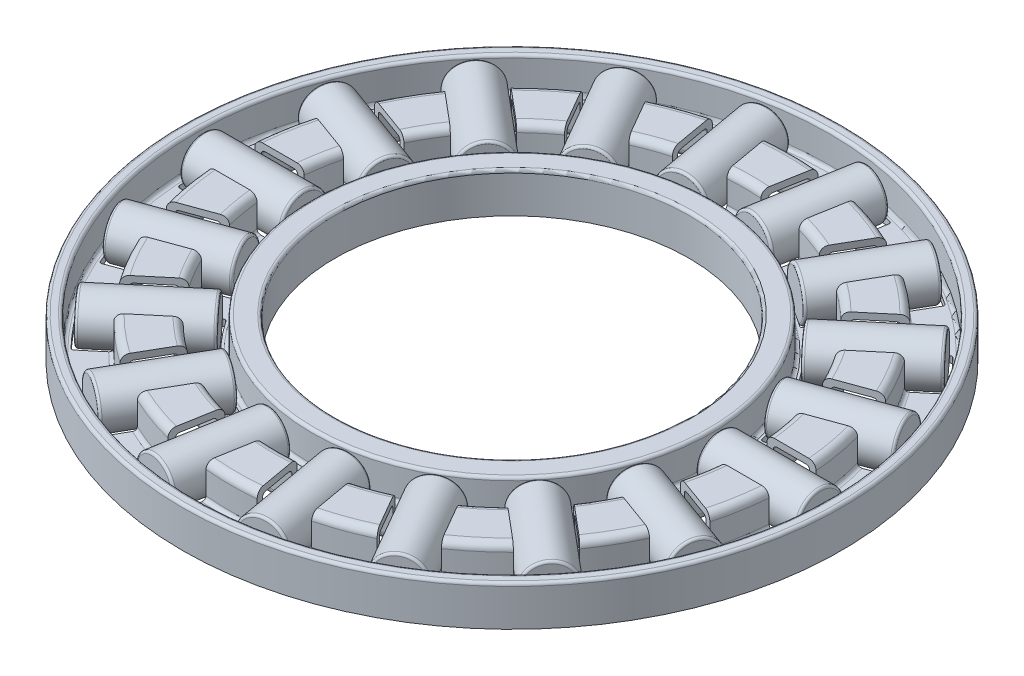
SolidWorks part; units mm, degrees
material "Plain Carbon Steel"
ref_plane "Front Plane" through (0, 0, 0) normal (0, 0, 1) x (1, 0, 0)
ref_plane "Top Plane" through (0, 0, 0) normal (0, 1, 0) x (1, 0, 0)
ref_plane "Right Plane" through (0, 0, 0) normal (1, 0, 0) x (0, 0, -1)
sketch "Sketch1" plane through (0, 0, 0) normal (1, 0, 0) x (0, 0, -1)
  line L0 (-14, 0) -> (14, 0) construction
  line L1 (-7.516, 0) -> (7.516, 0) construction
  line L2 (14, -1) -> (14, 1) construction
  line L3 (7.516, -0.85) -> (7.516, 0.85) construction
  line L4 (7.516, -0.85) -> (7.844, -0.85) construction
  line L5 (7.844, -0.85) -> (7.844, 0.577) construction
  line L6 (7.844, 0.577) -> (8.172, 0.577) construction
  line L7 (8.172, 0.577) -> (8.172, -0.85) construction
  line L8 (8.172, -0.85) -> (10.1501, -0.85) construction
  line L9 (10.1501, -0.85) -> (10.1501, 0.577) construction
  line L10 (10.1501, 0.577) -> (11.6886, 0.577) construction
  line L11 (11.6886, 0.577) -> (11.6886, -0.85) construction
  line L12 (11.6886, -0.85) -> (13.6667, -0.85) construction
  line L13 (13.6667, -0.85) -> (13.6667, 0.577) construction
  line L14 (13.6667, 0.577) -> (13.8333, 0.577) construction
  line L15 (7.516, 0.85) -> (8.5, 0.85) construction
  line L16 (8.5, 0.85) -> (8.5, -0.577) construction
  line L17 (8.5, -0.577) -> (9.8771, -0.577) construction
  line L18 (9.8771, -0.577) -> (9.8771, 0.85) construction
  line L19 (9.8771, 0.85) -> (11.9615, 0.85) construction
  line L20 (11.9615, 0.85) -> (11.9615, -0.577) construction
  line L21 (11.9615, -0.577) -> (13.5, -0.577) construction
  line L22 (13.5, -0.577) -> (13.5, 0.85) construction
  line L23 (13.5, 0.85) -> (14, 0.85) construction
  line L24 (10.1501, 0.577) -> (9.8771, 0.577) construction
  line L25 (8.172, 0.577) -> (8.172, 0.85) construction
  line L26 (11.6886, 0.577) -> (11.9615, 0.577) construction
  line L27 (8.5, -0.577) -> (8.5, -0.85) construction
  line L28 (8.5, -0.577) -> (8.172, -0.577) construction
  line L29 (13.6667, 0.577) -> (13.5, 0.577) construction
  line L30 (13.8333, 0.577) -> (13.8333, -0.85) construction
  line L31 (13.8333, -0.85) -> (14, -0.85) construction
  line L32 (0, 1) -> (0, -1) construction
  line L33 (-8.5, 1) -> (8.5, 1) construction
  line L34 (-13.5, 0.85) -> (13.5, 0.85) construction
  line L35 (13.8333, 0.577) -> (14, 0.577) construction
  line L36 (9.8771, -0.577) -> (9.8771, -0.85) construction
  line L37 (11.6886, 0.577) -> (11.6886, 0.85) construction
  line L38 (7.844, -0.577) -> (7.516, -0.577) construction
  line L39 (8.172, -0.577) -> (7.844, -0.577) construction
  point P4 (0, 0)
  point P8 (0, 0)
  point P11 (14, 0)
  point P14 (7.516, 0)
  point P45 (0, 1)
  point P48 (0, 0)
  point P49 (0, 1)
  point P55 (0, 0.85)
  dimension "OD" = 28
  dimension "ID" = 15.032
  dimension "Thickness" = 2
  dimension "Approx. Raceway Thickness" = 1.7
  dimension "Inner Raceway" = 17
  dimension "Outer Raceway" = 27
  dimension "Approx. Raceway Notch Width" = 1.5385
  dimension "D3" = 1.5385
sketch "Sketch2" plane through (0, 0, 0) normal (0, 1, 0) x (1, 0, 0)
  line L0 (8.5, 0) -> (13.5, 0) construction
  line L1 (13.25, 0) -> (8.75, 0)
  line L2 (13.2122, -1) -> (8.6927, -1)
  line L3 (13.2122, 1) -> (8.6927, 1)
  circle A0 centre (0, 0) radius 7.516
  circle A1 centre (0, 0) radius 8.5
  circle A2 centre (0, 0) radius 13.5
  circle A3 centre (0, 0) radius 14
  arc A4 (8.6927, -1) -> (8.6927, 1) centre (0, 0) ccw
  arc A5 (13.2122, -1) -> (13.2122, 1) centre (0, 0) ccw
  arc A6 (13.2122, 1) -> (12.9547, 2.7818) centre (0, 0) ccw
  point P15 (11, 0)
  dimension "Approx. Roller Length" = 4.5
  dimension "Roller Thickness" = 2
  dimension "Roller Arc Length" = 2.0019
  dimension "Approx. Roller Gap" = 1.8017
sketch "Sketch3" plane through (0, 0, 0) normal (1, 0, 0) x (0, 0, -1)
  line L0 (7.844, -0.85) -> (7.844, 0.577)
  line L1 (7.844, 0.577) -> (8.172, 0.577)
  line L2 (8.172, 0.577) -> (8.172, -0.85)
  line L3 (8.172, -0.85) -> (10.1501, -0.85)
  line L4 (10.1501, -0.85) -> (10.1501, 0.577)
  line L5 (10.1501, 0.577) -> (11.6886, 0.577)
  line L6 (11.6886, 0.577) -> (11.6886, -0.85)
  line L7 (11.6886, -0.85) -> (13.6667, -0.85)
  line L8 (13.6667, -0.85) -> (13.6667, 0.577)
  line L9 (13.6667, 0.577) -> (13.8333, 0.577)
  line L10 (13.8333, 0.577) -> (13.8333, -0.85)
  line L11 (13.8333, -0.85) -> (14, -0.85)
  line L12 (14, -0.85) -> (14, 0.85)
  line L13 (14, 0.85) -> (13.5, 0.85)
  line L14 (13.5, 0.85) -> (13.5, -0.577)
  line L15 (13.5, -0.577) -> (11.9615, -0.577)
  line L16 (11.9615, -0.577) -> (11.9615, 0.85)
  line L17 (11.9615, 0.85) -> (9.8771, 0.85)
  line L18 (9.8771, 0.85) -> (9.8771, -0.577)
  line L19 (9.8771, -0.577) -> (8.5, -0.577)
  line L20 (8.5, -0.577) -> (8.5, 0.85)
  line L21 (8.5, 0.85) -> (7.516, 0.85)
  line L22 (7.516, 0.85) -> (7.516, -0.85)
  line L23 (7.516, -0.85) -> (7.844, -0.85)
revolve "Revolve1" add sketch "Sketch3" angle 360 about L32
fillet "Fillet1" radius 0.3077 4 edges at (0, -0.85, 11.6886) (0, -0.85, 13.6667) (0, -0.85, 8.172) (0, -0.85, 10.1501)
fillet "Fillet2" radius 0.3077 2 edges at (0, 0.85, 11.9615) (0, 0.85, 9.8771)
fillet "Fillet3" radius 0.125 4 edges at (0, 0.85, 13.5) (0, 0.85, 14) (0, 0.85, 8.5) (0, 0.85, 7.516)
fillet "Fillet4" radius 0.1538 6 edges at (0, 0.577, 10.1501) (0, 0.577, 11.6886) (0, -0.577, 13.5) (0, -0.577, 11.9615) (0, -0.577, 9.8771) (0, -0.577, 8.5)
sketch "Sketch4" plane through (0, 0, 0) normal (0, 1, 0) x (1, 0, 0)
  line L0 (8.6927, 1) -> (13.2122, 1)
  line L1 (8.6927, -1) -> (13.2122, -1)
  arc A0 (8.6927, -1) -> (8.6927, 1) centre (0, 0) ccw construction
  arc A1 (8.6927, -1) -> (8.6927, 1) centre (0, 0) ccw
  arc A2 (13.2122, -1) -> (13.2122, 1) centre (0, 0) ccw construction
  arc A3 (13.2122, -1) -> (13.2122, 1) centre (0, 0) ccw
extrude "Cut-Extrude1" cut sketch "Sketch4" against normal through all both and the other way through all
fillet "Fillet5" radius 0.1001 4 edges at (13.2122, -0.7135, -1) (13.2122, -0.7135, 1) (8.6927, -0.7135, -1) (8.6927, -0.7135, 1)
pattern_circular "CirPattern1" count 18 over 360 about axis through (0, 1, 0) along (0, -1, 0) of "Cut-Extrude1", "Fillet5"
sketch "Sketch5" plane through (0, 0, 0) normal (0, 1, 0) x (1, 0, 0)
  line L0 (8.8042, 0) -> (8.8042, 1)
  line L2 (8.8042, 1) -> (13.1191, 1)
  line L3 (13.1191, 1) -> (13.1191, 0)
  line L4 (13.1191, 0) -> (8.8042, 0)
  line L5 (13.25, 0) -> (8.75, 0) construction
revolve "Revolve2" add sketch "Sketch5" angle 360 about L1
fillet "Fillet6" radius 0.1001 2 edges at (8.8042, 0, -1) (13.1191, 0, -1)
pattern_circular "CirPattern2" count 18 over 360 about axis through (0, 1, 0) along (0, -1, 0) of bodies 107
ref_axis "Center Axis 1" through (0, 1.65, 0) along (0, -1, 0)
ref_plane "Contact Plane 1" through (0, 1, 0) normal (0, 1, 0) x (1, 0, 0)
ref_plane "Contact Plane 2" through (0, -1, 0) normal (0, 1, 0) x (1, 0, 0)
equation "\"Approx. Raceway Thickness@Sketch1\" = \"Thickness@Sketch1\" * .85"
equation "\"Approx. Raceway Notch Width@Sketch1\" =  ( \"Outer Raceway@Sketch1\" - \"Inner Raceway@Sketch1\" )  / 6.5"
equation "\"D3@Sketch1\" = \"Approx. Raceway Notch Width@Sketch1\""
equation "\"D1@Fillet2\"=\"D1@Fillet1\""
equation "\"D1@Fillet3\"=(\"OD@Sketch1\"-\"Outer Raceway@Sketch1\")/8"
equation "\"D1@Fillet1\" = \"Approx. Raceway Notch Width@Sketch1\" * 2 / 10"
equation "\"D1@Fillet4\"=\"D1@Fillet2\"/2"
equation "\"Approx. Roller Length@Sketch2\" =  ( \"Outer Raceway@Sketch1\" - \"Inner Raceway@Sketch1\" )  / 2 * .9"
equation "\"Approx. Roller Gap@Sketch2\" = \"Roller Arc Length@Sketch2\" * .9"
equation "\"Raceway Diff\"= ( \"Outer Raceway@Sketch1\" - \"Inner Raceway@Sketch1\" )"
equation "\"Circumference\"= ( \"Inner Raceway@Sketch1\" + ( \"Raceway Diff\" / 2 ) ) * 3.14"
equation "\"Instances\"= int ( \"Circumference\" /  ( \"Roller Arc Length@Sketch2\" + \"Approx. Roller Gap@Sketch2\" )  ) "
equation "\"D1@CirPattern1\"=\"Instances\""
equation "\"D1@Fillet5\" = \"Roller Arc Length@Sketch2\" / 20"
equation "\"D1@Fillet6\" = \"Roller Arc Length@Sketch2\" / 20"
equation "\"D1@CirPattern2\" = \"D1@CirPattern1\""
equation "\"Roller Thickness@Sketch2\" = \"Thickness@Sketch1\""
